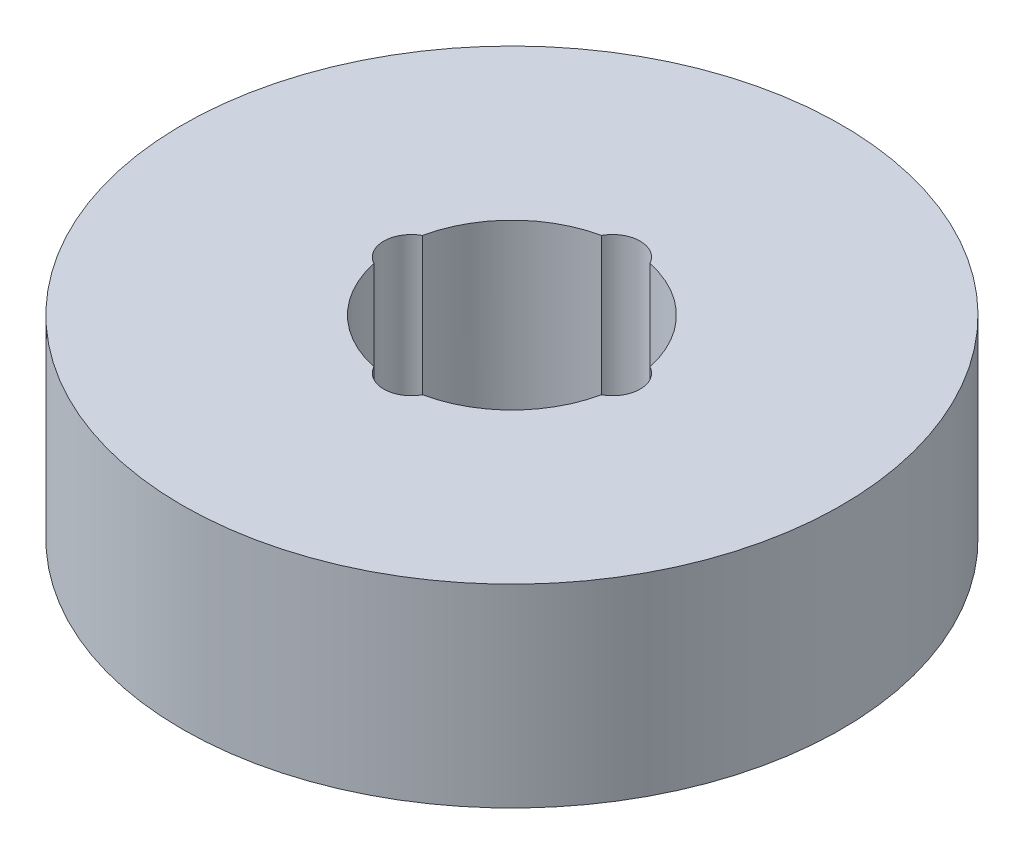
SolidWorks part; units mm, degrees
ref_plane "Front Plane" through (0, 0, 0) normal (0, 0, 1) x (1, 0, 0)
ref_plane "Top Plane" through (0, 0, 0) normal (0, 1, 0) x (1, 0, 0)
ref_plane "Right Plane" through (0, 0, 0) normal (1, 0, 0) x (0, 0, -1)
sketch "Sketch1" plane through (0, 0, 0) normal (0, 1, 0) x (1, 0, 0)
  circle A0 centre (0, 0) radius 42.5
  dimension "FLANGE_OD" = 85
extrude "Boss-Extrude1" add sketch "Sketch1" along normal blind 25
sketch "Sketch2" plane through (0, 0, 0) normal (0, 1, 0) x (1, 0, 0)
  circle A0 centre (0, 0) radius 15
  dimension "BORE_D" = 30
extrude "Cut-Extrude1" cut sketch "Sketch2" along normal through all
sketch "Sketch3" plane through (0, 25, 0) normal (0, 1, 0) x (1, 0, 0)
  circle A0 centre (0, 0) radius 12.9745 construction
  circle A1 centre (-12.9745, 0) radius 3.5589
  dimension "BOLT_D" = 7.1179
  dimension "BOLT_PCD" = 25.949
extrude "Cut-Extrude2" cut sketch "Sketch3" against normal blind 22.5502
pattern_circular "CirPattern1" count 4 over 360 about axis through (0, 0, 0) along (0, 1, 0) of "Cut-Extrude2"
